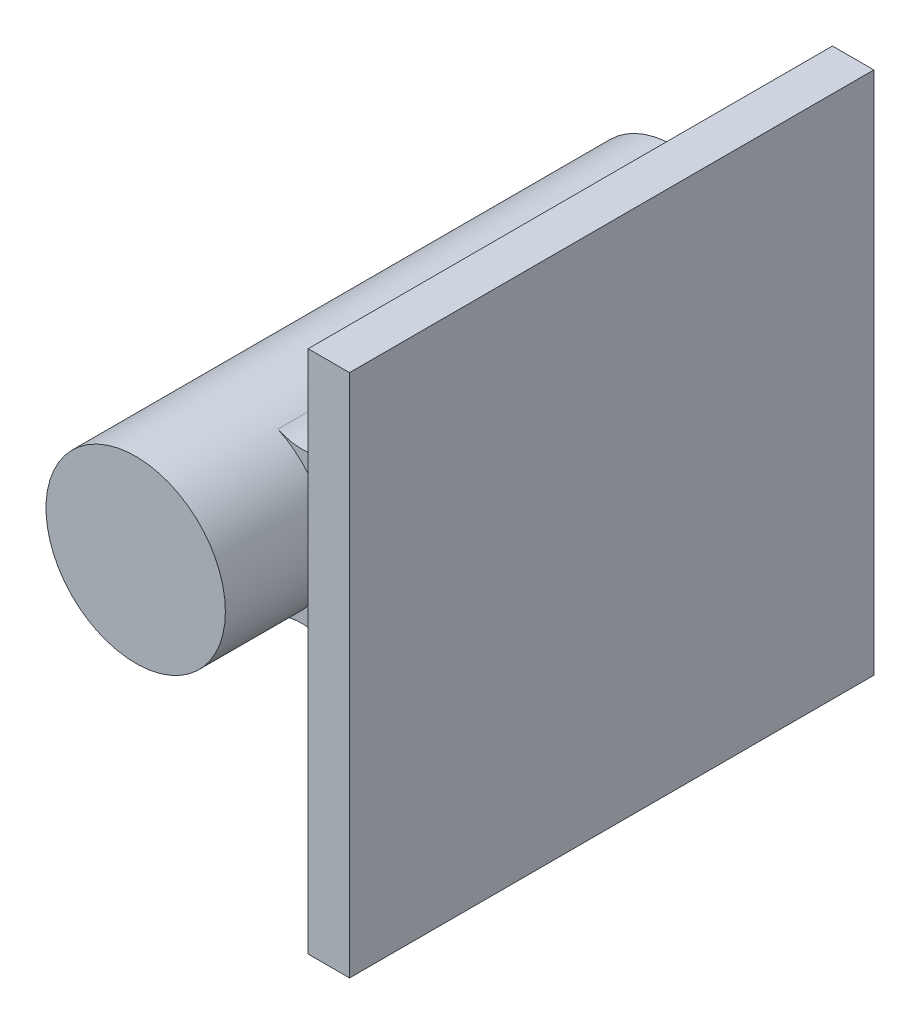
SolidWorks part; units mm, degrees
ref_plane "正面" through (0, 0, 0) normal (0, 0, 1) x (1, 0, 0)
ref_plane "平面" through (0, 0, 0) normal (0, 1, 0) x (1, 0, 0)
ref_plane "右側面" through (0, 0, 0) normal (1, 0, 0) x (0, 0, -1)
sketch "ｽｹｯﾁ1" plane through (0, 0, 0) normal (0, 0, 1) x (1, 0, 0)
  circle A0 centre (0, 0) radius 3.25
  dimension "D1" = 6.5
extrude "ﾎﾞｽ - 押し出し1" add sketch "ｽｹｯﾁ1" along normal blind 19.5
ref_plane "平面1" through (5, 0, 0) normal (1, 0, 0) x (0, 0, -1)
sketch "ｽｹｯﾁ2" plane through (5, 0, 0) normal (1, 0, 0) x (0, 0, -1)
  line L0 (-19.5, 0) -> (0, 0) construction
  line L1 (-19.5, 3.25) -> (-19.5, -3.25) construction
  line L3 (-3.75, -6) -> (-15.75, -6)
  line L4 (-3.75, -6) -> (-3.75, 6)
  line L5 (-3.75, 6) -> (-15.75, 6)
  line L6 (-15.75, -6) -> (-15.75, 6)
  line L7 (-3.75, -6) -> (-15.75, 6) construction
  line L8 (-3.75, 6) -> (-15.75, -6) construction
  point P5 (-9.75, 0)
  dimension "D1" = 12
  dimension "D2" = 12
extrude "ﾎﾞｽ - 押し出し2" add sketch "ｽｹｯﾁ2" along normal blind 1 separate body
sketch "ｽｹｯﾁ3" plane through (0, 0, 3.75) normal (0, 0, -1) x (-1, 0, 0)
  line L0 (0, 0) -> (-5, 4.5)
  line L1 (-5, 3.575) -> (-5, -3.575) construction
  line L2 (-5, 4.5) -> (-5, -4.5)
  line L3 (-5, -4.5) -> (0, 0)
  dimension "D1" = 9
extrude "ﾎﾞｽ - 押し出し3" add sketch "ｽｹｯﾁ3" against normal up to surface (12 mm away) up to face at (5.5, 0, 15.75)
fillet "ﾌｨﾚｯﾄ1" radius 2 4 edges at (5, -4.5, 9.75) (2.4157, -2.1741, 9.75) (2.4157, 2.1741, 9.75) (5, 4.5, 9.75)
sketch "ｽｹｯﾁ5" plane through (6, 0, 0) normal (1, 0, 0) x (0, 0, -1)
  line L0 (-15.75, 0) -> (-3.75, 0) construction
  line L1 (-15.75, 6) -> (-15.75, -6) construction
  line L2 (-3.75, -2.9305) -> (-3.75, 2.9305) construction
  line L4 (-0.25, -9.5) -> (-19.25, -9.5)
  line L5 (-0.25, -9.5) -> (-0.25, 9.5)
  line L6 (-0.25, 9.5) -> (-19.25, 9.5)
  line L7 (-19.25, -9.5) -> (-19.25, 9.5)
  line L8 (-0.25, -9.5) -> (-19.25, 9.5) construction
  line L9 (-0.25, 9.5) -> (-19.25, -9.5) construction
  point P6 (-9.75, 0)
  dimension "D1" = 19
  dimension "D2" = 19
extrude "ﾎﾞｽ - 押し出し4" add sketch "ｽｹｯﾁ5" along normal blind 1.5
